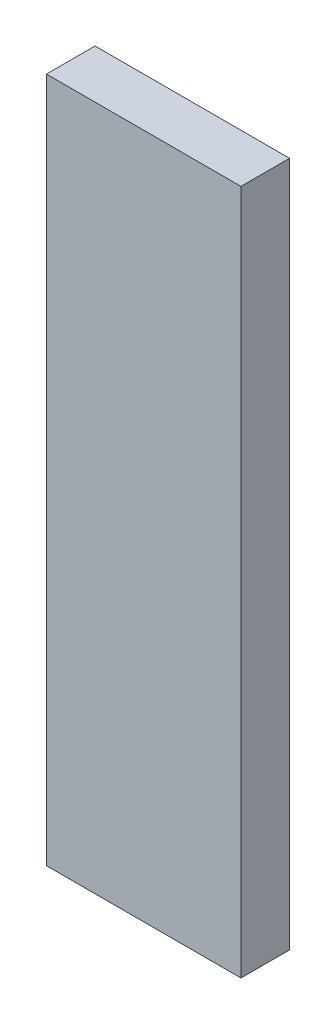
SolidWorks part; units mm, degrees
ref_plane "Front Plane" through (0, 0, 0) normal (0, 0, 1) x (1, 0, 0)
ref_plane "Top Plane" through (0, 0, 0) normal (0, 1, 0) x (1, 0, 0)
ref_plane "Right Plane" through (0, 0, 0) normal (1, 0, 0) x (0, 0, -1)
sketch "Sketch1" plane through (0, 0, 0) normal (0, 0, 1) x (1, 0, 0)
  line L0 (-100, 48.5073) -> (-80, 48.5073) construction
  line L1 (-100, -21.9927) -> (-80, -21.9927) construction
  line L2 (-100, 48.5073) -> (-80, 48.5073)
  line L3 (-100, -21.9927) -> (-80, -21.9927)
  line L4 (-100, -21.9927) -> (-100, 48.5073)
  line L5 (-80, 48.5073) -> (-80, -21.9927)
  point P5 (-80, 48.7573)
extrude "Boss-Extrude1" add sketch "Sketch1" along normal blind 5
